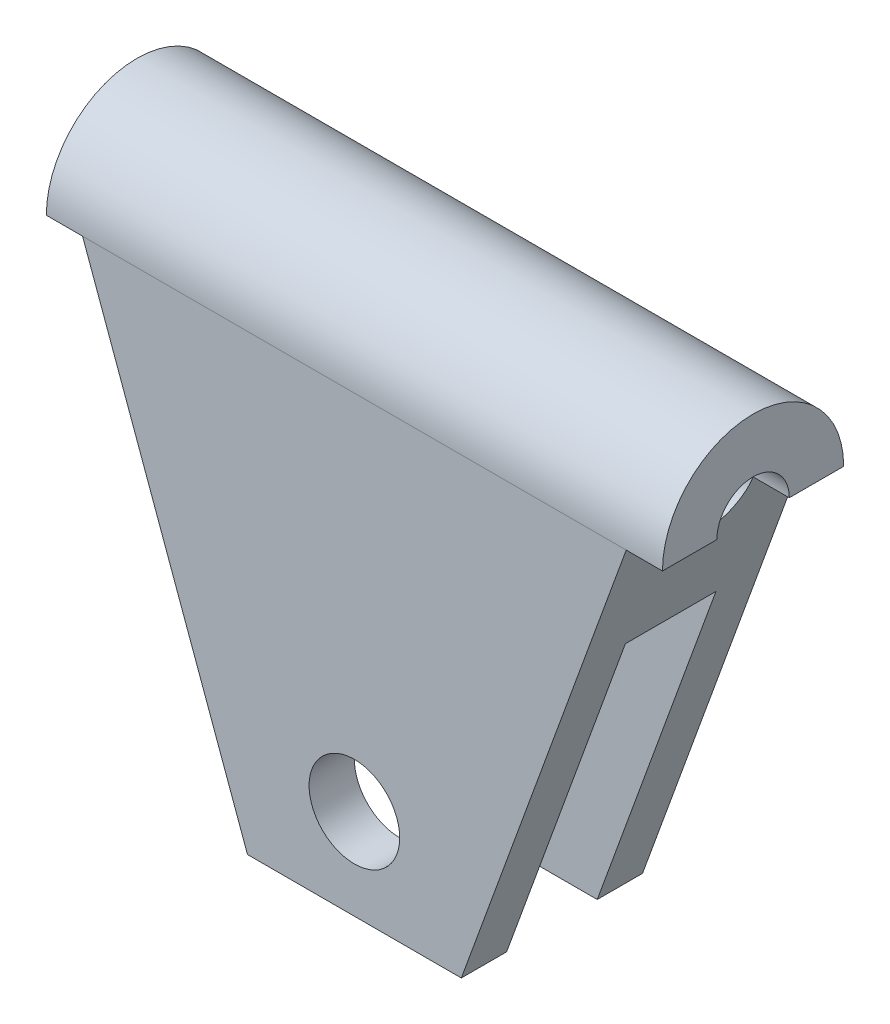
SolidWorks part; units mm, degrees
ref_plane "Front Plane" through (0, 0, 0) normal (0, 0, 1) x (1, 0, 0)
ref_plane "Top Plane" through (0, 0, 0) normal (0, 1, 0) x (1, 0, 0)
ref_plane "Right Plane" through (0, 0, 0) normal (1, 0, 0) x (0, 0, -1)
sketch "Sketch2" plane through (0, 0, 0) normal (0, 0, 1) x (1, 0, 0)
  line L0 (0, 0) -> (300, 0)
  line L1 (300, 0) -> (209.0074, -250)
  line L2 (209.0074, -250) -> (90.9926, -250)
  line L3 (90.9926, -250) -> (0, 0)
  dimension "D1" = 70
  dimension "D2" = 300
  dimension "D3" = 250
extrude "Boss-Extrude1" add sketch "Sketch2" along normal blind 100
sketch "Sketch3" plane through (0, 0, 0) normal (1, 0, 0) x (0, 0, -1)
  line L0 (-100, 0) -> (0, 0) construction
  line L1 (0, 0) -> (-30, 0)
  line L3 (-70, 0) -> (-100, 0)
  arc A0 (0, 0) -> (-100, 0) centre (-50, 0) ccw
  circle A1 centre (-50, 0) radius 20
  dimension "D1" = 40
extrude "Boss-Extrude2" add sketch "Sketch3" along normal blind 320 and the other way blind 20 contours A1 L1 A0 L3 | A1 region at (0, 23.6459, 50) region at (0, 0, 50)
extrude "Cut-Extrude1" cut sketch "Sketch3<3>" along normal through all both and the other way through all contours A1
sketch "Sketch3<3>" plane through (0, 0, 0) normal (1, 0, 0) x (0, 0, -1) same geometry as "Sketch3"
sketch "Sketch4" plane through (0, 0, 0) normal (1, 0, 0) x (0, 0, -1)
  line L0 (-100, -250) -> (0, -250) construction
  line L1 (-75, -250) -> (-25, -250)
  line L2 (-75, -250) -> (-75, -70)
  line L3 (-75, -70) -> (-25, -70)
  line L4 (-25, -250) -> (-25, -70)
  point P6 (-50, -250)
  point P7 (-50, -250)
  dimension "D1" = 50
  dimension "D2" = 180
extrude "Cut-Extrude2" cut sketch "Sketch4" against normal through all both and the other way through all
sketch "Sketch5" plane through (0, 0, 0) normal (0, 0, 1) x (1, 0, 0)
  line L0 (150, -200) -> (150, -250) construction
  line L1 (90.9926, -250) -> (209.0074, -250) construction
  line L2 (90.9926, -250) -> (209.0074, -250) construction
  circle A0 centre (150, -200) radius 25
  dimension "D1" = 50
  dimension "D2" = 50
extrude "Cut-Extrude5" cut sketch "Sketch5" along normal through all
ref_plane "Plane1" through (0, 0, 50) normal (0, 0, -1) x (-1, 0, 0)
